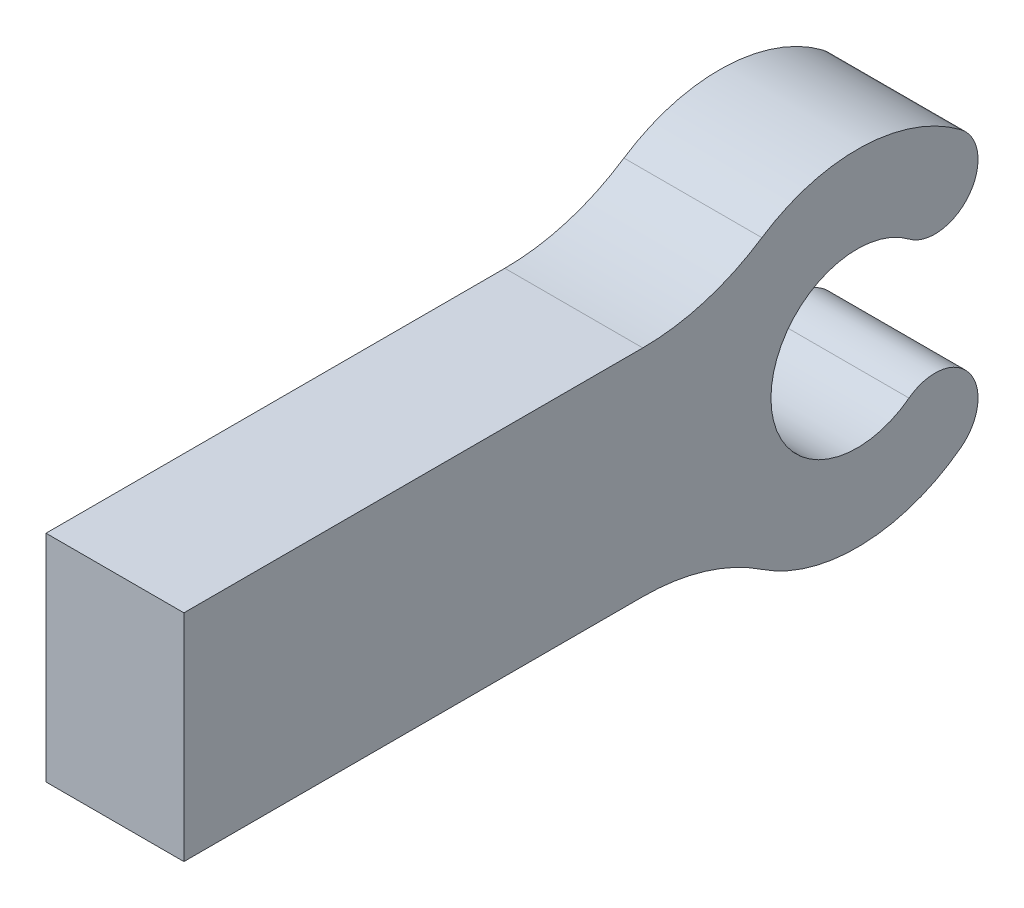
SolidWorks part; units mm, degrees
material "Delrin 2700 NC010, Low Viscosity Acetal Copolymer (SS)"
ref_plane "Front Plane" through (0, 0, 0) normal (0, 0, 1) x (1, 0, 0)
ref_plane "Top Plane" through (0, 0, 0) normal (0, 1, 0) x (1, 0, 0)
ref_plane "Right Plane" through (0, 0, 0) normal (1, 0, 0) x (0, 0, -1)
sketch "Sketch1" plane through (0, 0, 0) normal (1, 0, 0) x (0, 0, -1)
  line L0 (0, 1.27) -> (10.4547, 1.27) construction
  line L1 (0, 0) -> (6.35, 0)
  line L2 (0, 0) -> (0, 2.54)
  line L3 (0, 2.54) -> (6.35, 2.54)
  line L4 (7.9362, 1.27) -> (9.1591, 2.8928) construction
  line L5 (7.9362, 1.27) -> (9.1591, -0.3528) construction
  arc A0 (9.1591, 2.8928) -> (6.35, 2.54) centre (7.9362, 1.27) ccw
  arc A1 (8.5477, 2.0814) -> (8.5477, 0.4586) centre (7.9362, 1.27) ccw
  arc A2 (9.1591, 2.8928) -> (8.5477, 2.0814) centre (8.8534, 2.4871) cw
  arc A3 (8.5477, 0.4586) -> (9.1591, -0.3528) centre (8.8534, 0.0529) cw
  arc A4 (6.35, 0) -> (9.1591, -0.3528) centre (7.9362, 1.27) ccw
  dimension "D3" = 2.032
  dimension "D4" = 4.064
  dimension "D1" = 2.54
  dimension "D2" = 6.35
  dimension "D5" = 53
extrude "Boss-Extrude1" add sketch "Sketch1" along normal blind 1.6256
fillet "Fillet1" radius 2.54 2 edges at (0.8128, 0, -6.35) (0.8128, 2.54, -6.35)
